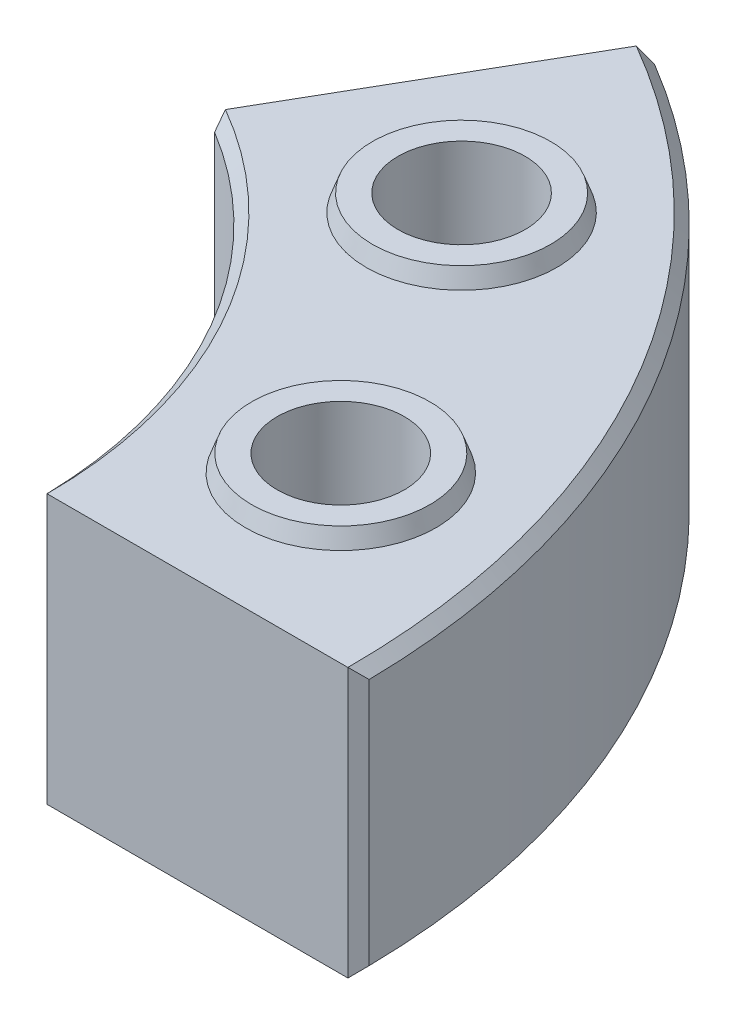
SolidWorks part; units mm, degrees
ref_plane "Front Plane" through (0, 0, 0) normal (0, 0, 1) x (1, 0, 0)
ref_plane "Top Plane" through (0, 0, 0) normal (0, 1, 0) x (1, 0, 0)
ref_plane "Right Plane" through (0, 0, 0) normal (1, 0, 0) x (0, 0, -1)
sketch "Sketch1" plane through (0, 0, 0) normal (0, 1, 0) x (1, 0, 0)
  line L0 (0, 0) -> (0, 50000) construction
  line L1 (0, 0) -> (50000, 0) construction
  line L10 (0, 225) -> (0, 50225) construction
  line L12 (225, 0) -> (377, 0) construction
  line L13 (225, 0) -> (377, 0)
  line L14 (0, 0) -> (25000, 43301.2702) construction
  line L15 (0, 0) -> (12940.9523, 48296.2913) construction
  line L16 (0, 0) -> (35355.3391, 35355.3391) construction
  line L17 (0, 0) -> (48296.2913, 12940.9523) construction
  line L18 (188.5, 326.4916) -> (112.5, 194.8557)
  arc A6 (225, 0) -> (112.5, 194.8557) centre (0, 0) ccw
  arc A7 (377, 0) -> (188.5, 326.4916) centre (0, 0) ccw
  arc A8 (301, 0) -> (150.5, 260.6736) centre (0, 0) ccw construction
  circle A10 centre (212.8391, 212.8391) radius 30
  circle A11 centre (290.7437, 77.9045) radius 30
  arc A13 (106.4594, 281.5447) -> (0, 301) centre (0, 0) ccw construction
  dimension "D1" = 450
  dimension "D2" = 754
  dimension "D4" = 15
  dimension "D5" = 602
  dimension "D7" = 15
  dimension "D9" = 60
  dimension "D10" = 60
  dimension "D3" = 30
  dimension "D8" = 30
extrude "Boss-Extrude1" add sketch "Sketch1" against normal blind 127
sketch "Sketch2" plane through (0, 0, 0) normal (0, 1, 0) x (1, 0, 0)
  circle A0 centre (212.8391, 212.8391) radius 30
  circle A1 centre (290.7437, 77.9045) radius 30
  circle A2 centre (212.8391, 212.8391) radius 45
  circle A3 centre (290.7437, 77.9045) radius 45
  dimension "D1" = 90
  dimension "D2" = 60
  dimension "D3" = 90
  dimension "D4" = 60
extrude "Boss-Extrude2" add sketch "Sketch2" along normal blind 8
chamfer "Chamfer1" distance 8 angle 20 2 edges at (290.7437, 8, -32.9045) (212.8391, 8, -167.8391)
sketch "Sketch3" plane through (0, -127, 0) normal (0, -1, 0) x (1, 0, 0)
  circle A0 centre (290.7437, -77.9045) radius 46
  circle A1 centre (290.7437, -77.9045) radius 30
  circle A2 centre (212.8391, -212.8391) radius 46
  circle A3 centre (212.8391, -212.8391) radius 30
  dimension "D1" = 60
  dimension "D2" = 60
  dimension "D3" = 92
  dimension "D4" = 92
extrude "Cut-Extrude1" cut sketch "Sketch3" against normal blind 10
chamfer "Chamfer2" distance 10 angle 20 2 edges at (212.8391, -117, -258.8391) (290.7437, -117, -123.9045)
chamfer "Chamfer3" distance 5 8 edges at (225, -63.5, 0) (194.8557, -127, -112.5) (112.5, -63.5, -194.8557) (194.8557, 0, -112.5) (188.5, -63.5, -326.4916) (326.4916, -127, -188.5) (377, -63.5, 0) (326.4916, 0, -188.5)
